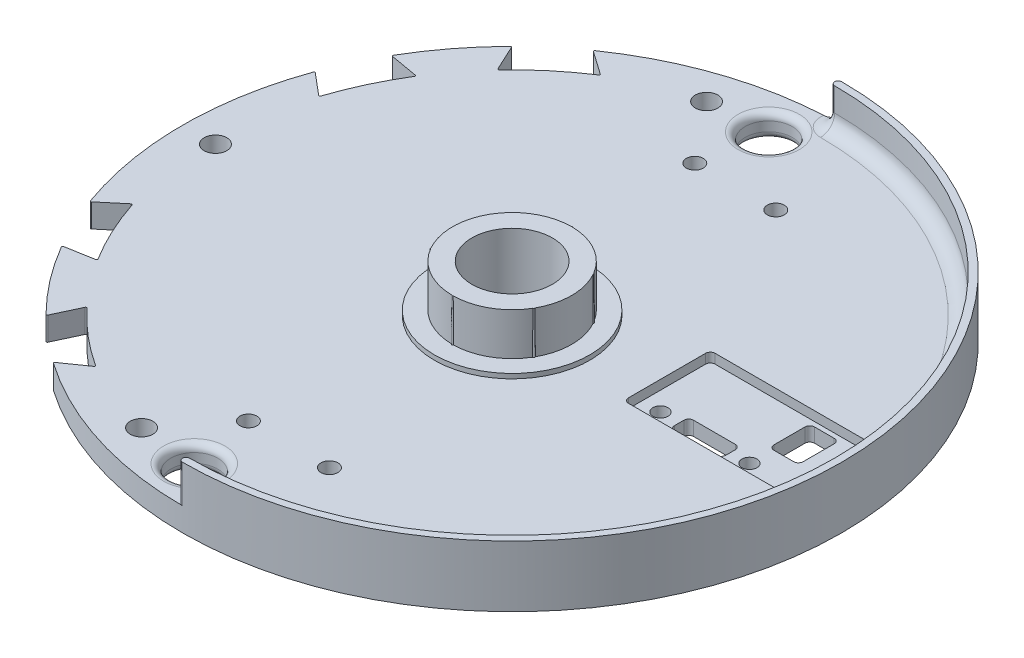
SolidWorks part; units mm, degrees
ref_plane "Front Plane" through (0, 0, 0) normal (0, 0, 1) x (1, 0, 0)
ref_plane "Top Plane" through (0, 0, 0) normal (0, 1, 0) x (1, 0, 0)
ref_plane "Right Plane" through (0, 0, 0) normal (1, 0, 0) x (0, 0, -1)
sketch "Sketch1" plane through (0, 0, 0) normal (0, 1, 0) x (1, 0, 0)
  circle A0 centre (0, 0) radius 70
  dimension "D1" = 140
extrude "base-plate" add sketch "Sketch1" along normal blind 5
sketch "Sketch2" plane through (0, 5, 0) normal (0, 1, 0) x (1, 0, 0)
  circle A0 centre (0, 0) radius 16.5
  dimension "D1" = 33
extrude "bearing-stepup" add sketch "Sketch2" along normal blind 1
sketch "Sketch3" plane through (0, 6, 0) normal (0, 1, 0) x (1, 0, 0)
  circle A0 centre (0, 0) radius 12.65
  dimension "D1" = 25.3
extrude "bearing-sitting" add sketch "Sketch3" along normal blind 9
sketch "Sketch4" plane through (0, 6, 0) normal (0, 1, 0) x (1, 0, 0)
  circle A10 centre (0, 12.55) radius 0.25
  circle A11 centre (0, 0) radius 12.55 construction
  circle A15 centre (0, 0) radius 12.65 construction
  circle A19 centre (10.8686, 6.275) radius 0.25
  circle A20 centre (10.8686, -6.275) radius 0.25
  circle A21 centre (0, -12.55) radius 0.25
  circle A22 centre (-10.8686, -6.275) radius 0.25
  circle A23 centre (-10.8686, 6.275) radius 0.25
  point P19 (0, 0)
  dimension "D1" = 0.5
  dimension "D3" = 0.1
  dimension "D2" = 6
extrude "bearing-sitting-grid" add sketch "Sketch4" along normal up to surface (9 mm away) draft 0.5
sketch "Sketch5" plane through (0, 0, 0) normal (0, -1, 0) x (1, 0, 0)
  line L2 (2.75, 0) -> (-2.75, 0) construction
  circle A0 centre (-18.7, 60) radius 2.4
  circle A1 centre (-63, 0) radius 2.4
  circle A2 centre (-18.7, -60) radius 2.4
  dimension "D3" = 4.8
  dimension "D4" = 4.8
  dimension "D1" = 63
  dimension "D2" = 60
  dimension "D5" = 18.7
extrude "m4-screw-clearance-holes" cut sketch "Sketch5" against normal through all
sketch "Sketch6" plane through (0, 0, 0) normal (0, -1, 0) x (1, 0, 0)
  line L0 (2.75, 0) -> (-2.75, 0) construction
  circle A0 centre (-6.5, 61) radius 5
  circle A1 centre (-6.5, -61) radius 5
  dimension "D3" = 10
  dimension "D1" = 61
  dimension "D2" = 6.5
extrude "holes-reserved-for-rods" cut sketch "Sketch6" against normal through all
sketch "Sketch8" plane through (0, 15, 0) normal (0, 1, 0) x (1, 0, 0)
  circle A0 centre (0, 0) radius 8.55
  dimension "D1" = 17.1
extrude "Cut-Extrude1" cut sketch "Sketch8" against normal through all
sketch "Sketch9" plane through (0, 5, 0) normal (0, 1, 0) x (1, 0, 0)
  line L0 (0, -2.75) -> (0, 2.75) construction
  line L1 (-2.75, 0) -> (2.75, 0) construction
  circle A0 centre (-8.6, 47.4) radius 1.8
  circle A1 centre (8.6, 47.4) radius 1.8
  circle A2 centre (8.6, -47.4) radius 1.8
  circle A3 centre (-8.6, -47.4) radius 1.8
  dimension "D1" = 3.6
  dimension "D2" = 8.6
  dimension "D3" = 47.4
extrude "Cut-Extrude2" cut sketch "Sketch9" against normal up to next
sketch "Sketch10" plane through (0, 5, 0) normal (0, 1, 0) x (1, 0, 0)
  line L0 (-34.9731, 53.5993) -> (-40.2333, 57.2825)
  line L1 (-46.712, 43.7492) -> (-49.4258, 49.569)
  line L2 (-49.4258, 49.569) -> (-40.2333, 57.2825) construction
  line L3 (-2.75, 0) -> (2.75, 0) construction
  line L6 (-44.8295, 53.4258) -> (0, 0) construction
  line L7 (0, 0) -> (0, 21.039) construction
  line L8 (-35.0368, 53.7659) -> (-40.2333, 57.4046)
  line L9 (-46.865, 43.8408) -> (-49.5461, 49.5903)
  line L10 (-54.4765, 33.9213) -> (-60.724, 35.0229)
  line L11 (-61.0021, 19.9273) -> (-65.8617, 24.005)
  line L12 (0, 0) -> (-34.7944, 53.5962) construction
  line L13 (0, 0) -> (-54.1852, 33.8699) construction
  line L14 (-46.74, 43.5727) -> (-49.5461, 49.5903) construction
  line L15 (-34.7944, 53.5962) -> (-40.2333, 57.4046) construction
  line L16 (-61.0021, -19.9273) -> (-65.8617, -24.005)
  line L17 (-54.4765, -33.9213) -> (-60.724, -35.0229)
  line L18 (-46.865, -43.8408) -> (-49.5461, -49.5903)
  line L19 (-35.0368, -53.7659) -> (-40.2333, -57.4046)
  circle A1 centre (0, 0) radius 70 construction
  arc A2 (-34.9731, 53.5993) -> (-46.712, 43.7492) centre (0, 0) ccw
  arc A5 (-40.2333, 57.4046) -> (-49.5461, 49.5903) centre (0, 0) ccw
  arc A6 (-35.0418, 53.4348) -> (-46.5381, 43.7883) centre (0, 0) ccw
  arc A7 (-60.724, 35.0229) -> (-65.8617, 24.005) centre (0, 0) ccw
  arc A8 (-54.3412, 33.6191) -> (-60.6836, 20.0178) centre (0, 0) ccw
  arc A9 (-40.2333, 57.2825) -> (-49.4258, 49.569) centre (0, 0) ccw construction
  arc A10 (-61.0021, 19.9273) -> (-60.6836, 20.0178) centre (-60.8735, 20.0805) ccw
  arc A11 (-54.4765, 33.9213) -> (-54.3412, 33.6191) centre (-54.5113, 33.7243) cw
  arc A12 (-34.7944, 53.5962) -> (-46.74, 43.5727) centre (0, 0) ccw construction
  arc A13 (-46.865, 43.8408) -> (-46.5381, 43.7883) centre (-46.6838, 43.9253) ccw
  arc A14 (-35.0368, 53.7659) -> (-35.0418, 53.4348) centre (-35.1515, 53.6021) cw
  arc A15 (-35.0368, -53.7659) -> (-35.0418, -53.4348) centre (-35.1515, -53.6021) ccw
  arc A16 (-46.865, -43.8408) -> (-46.5381, -43.7883) centre (-46.6838, -43.9253) cw
  arc A17 (-54.4765, -33.9213) -> (-54.3412, -33.6191) centre (-54.5113, -33.7243) ccw
  arc A18 (-61.0021, -19.9273) -> (-60.6836, -20.0178) centre (-60.8735, -20.0805) cw
  arc A19 (-54.3412, -33.6191) -> (-60.6836, -20.0178) centre (0, 0) cw
  arc A20 (-60.724, -35.0229) -> (-65.8617, -24.005) centre (0, 0) cw
  arc A21 (-35.0418, -53.4348) -> (-46.5381, -43.7883) centre (0, 0) cw
  arc A22 (-40.2333, -57.4046) -> (-49.5461, -49.5903) centre (0, 0) cw
  point P30 (-54.1852, 33.8699)
  circle M14 centre (0, 0) radius 70
  dimension "D3" = 64
  dimension "D4" = 40
  dimension "D9" = 0.2
  dimension "D1" = 105
  dimension "D2" = 105
  dimension "D5" = 12
  dimension "D8" = 25
  dimension "D6" = 0.1
  dimension "D7" = 2
extrude "Cut-Extrude3" cut sketch "Sketch10" against normal through all contours A6 L8 L0 A2 L1 L9 M14 | A2 L0 L1 M14 | L8 A5 L9 M14 | A8 L10 L11 M14 | L10 A7 L11 M14 | A17 A19 A18 L16 L17 M14 | A20 L17 L16 M14 | A15 A21 A16 L18 L19 M14 | A22 L19 L18 M14
sketch "Sketch11" plane through (0, 5, 0) normal (0, 1, 0) x (1, 0, 0)
  arc A0 (0, 69.25) -> (0, -69.25) centre (0, 0) cw construction
  arc A1 (0, -70) -> (0, 70) centre (0, 0) ccw
  arc A2 (0, -68.5) -> (0, 68.5) centre (0, 0) ccw
  arc A3 (0, -68.5) -> (0, -70) centre (0, -69.25) ccw
  arc A4 (0, 70) -> (0, 68.5) centre (0, 69.25) ccw
  point P4 (69.25, 0)
  dimension "D1" = 70
  dimension "D2" = 1.5
extrude "Boss-Extrude1" add sketch "Sketch11" along normal blind 8
sketch "Sketch12" plane through (0, 5, 0) normal (0, 1, 0) x (1, 0, 0)
  line L0 (31.5, 0) -> (50.4, 0) construction
  line L1 (50.6, 5.0117) -> (54.8, 5.0117)
  line L2 (49.6, 6.0117) -> (49.6, 12.6117)
  line L3 (50.6, 13.6117) -> (54.8, 13.6117)
  line L4 (55.8, 6.0117) -> (55.8, 12.6117)
  line L6 (36.5, 2) -> (45.4, 2)
  line L7 (35.5, 1) -> (35.5, -1)
  line L8 (36.5, -2) -> (45.4, -2)
  line L9 (46.4, 1) -> (46.4, -1)
  circle A0 centre (31.5, 0) radius 1.6
  circle A1 centre (50.4, 0) radius 1.6
  arc A3 (35.5, -1) -> (36.5, -2) centre (36.5, -1) ccw
  arc A4 (36.5, 2) -> (35.5, 1) centre (36.5, 1) ccw
  arc A5 (45.4, -2) -> (46.4, -1) centre (45.4, -1) ccw
  arc A6 (45.4, 2) -> (46.4, 1) centre (45.4, 1) cw
  arc A7 (50.6, 5.0117) -> (49.6, 6.0117) centre (50.6, 6.0117) cw
  arc A8 (54.8, 5.0117) -> (55.8, 6.0117) centre (54.8, 6.0117) ccw
  arc A9 (54.8, 13.6117) -> (55.8, 12.6117) centre (54.8, 12.6117) cw
  arc A10 (49.6, 12.6117) -> (50.6, 13.6117) centre (50.6, 12.6117) cw
  point P9 (52.7, 5.0117)
  point P14 (35.5, 0)
  point P21 (46.4, -2)
  point P24 (46.4, 2)
  point P29 (55.8, 5.0117)
  point P32 (55.8, 13.6117)
  point P35 (49.6, 13.6117)
  dimension "D1" = 3.2
  dimension "D2" = 3.2
  dimension "D11" = 1
  dimension "D3" = 18.9
  dimension "D4" = 31.5
  dimension "D5" = 8.6
  dimension "D6" = 6.2
  dimension "D7" = 2.3
  dimension "D8" = 4
  dimension "D9" = 4
  dimension "D10" = 4
extrude "Cut-Extrude4" cut sketch "Sketch12" against normal through all
sketch "Sketch13" plane through (0, 5, 0) normal (0, 1, 0) x (1, 0, 0)
  line L1 (28.5, -3.8) -> (66.5, -3.8)
  line L2 (27.5, -2.8) -> (27.5, 13.6)
  line L3 (28.5, 14.6) -> (66.5, 14.6)
  line L4 (67.5, -2.8) -> (67.5, 13.6)
  circle A0 centre (31.5, 0) radius 1.6 construction
  arc A1 (28.5, -3.8) -> (27.5, -2.8) centre (28.5, -2.8) cw
  arc A2 (66.5, -3.8) -> (67.5, -2.8) centre (66.5, -2.8) ccw
  arc A3 (66.5, 14.6) -> (67.5, 13.6) centre (66.5, 13.6) cw
  arc A4 (27.5, 13.6) -> (28.5, 14.6) centre (28.5, 13.6) cw
  point P8 (27.5, -3.8)
  point P11 (67.5, -3.8)
  point P16 (27.5, 14.6)
  dimension "D1" = 3.8
  dimension "D2" = 4
  dimension "D5" = 1
  dimension "D3" = 40
  dimension "D4" = 18.4
extrude "Cut-Extrude5" cut sketch "Sketch13" against normal blind 2
fillet "Fillet1" radius 3 2 edges at (-0.75, 5, -69.25) (43.0084, 5, -53.3153)
fillet "Fillet2" radius 0.2 8 edges at (-49.5011, 2.5, 49.4939) (-40.1462, 2.5, 57.3436) (-65.7802, 2.5, 23.9366) (-60.6192, 2.5, 35.0044) (-60.6192, 2.5, -35.0044) (-65.7802, 2.5, -23.9366) (-49.5011, 2.5, -49.4939) (-40.1462, 2.5, -57.3436)
fillet "Fillet3" radius 1.5 4 edges at (-6.5, 0, 56) (-6.5, 5, 66) (-6.5, 0, -56) (-6.5, 5, -56)
